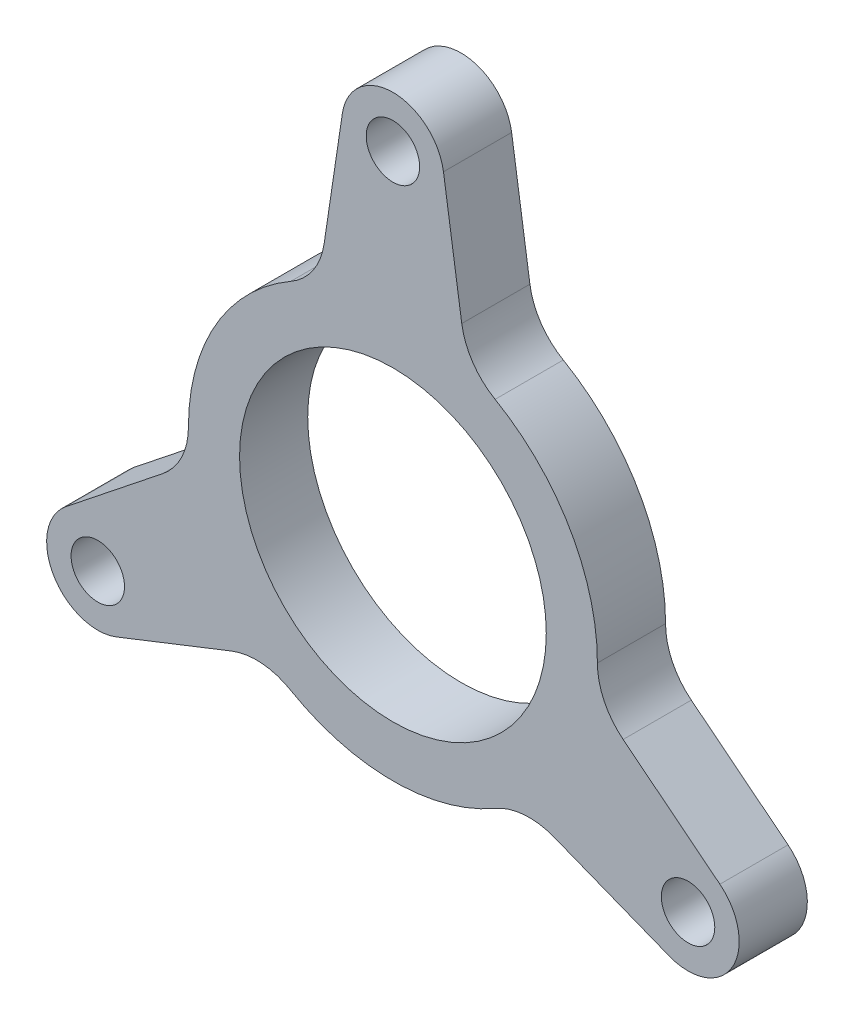
SolidWorks part; units mm, degrees
material "6061-T6 (SS)"
ref_plane "Front Plane" through (0, 0, 0) normal (0, 0, 1) x (1, 0, 0)
ref_plane "Top Plane" through (0, 0, 0) normal (0, 1, 0) x (1, 0, 0)
ref_plane "Right Plane" through (0, 0, 0) normal (1, 0, 0) x (0, 0, -1)
sketch "Sketch2" plane through (0, 0, 0) normal (0, 0, 1) x (1, 0, 0)
  line L3 (-4.7102, 32.4539) -> (-6.9072, 17.7537)
  line L4 (4.7102, 32.4539) -> (6.9072, 17.7537)
  line L5 (30.461, -12.1478) -> (18.8287, -2.8951)
  line L6 (25.7508, -20.3061) -> (11.9216, -14.8586)
  line L7 (-25.7508, -20.3061) -> (-11.9216, -14.8586)
  line L8 (-30.461, -12.1478) -> (-18.8287, -2.8951)
  line L9 (0, 31.75) -> (0, 0) construction
  circle A0 centre (0, 0) radius 14.2875
  circle A1 centre (0, 31.75) radius 2.4892
  circle A2 centre (27.4963, -15.875) radius 2.4892
  circle A3 centre (-27.4963, -15.875) radius 2.4892
  circle A4 centre (27.4963, -15.875) radius 4.7625
  circle A5 centre (0, 31.75) radius 4.7625
  circle A6 centre (-27.4963, -15.875) radius 4.7625
  circle A7 centre (0, 0) radius 19.05
  point P11 (0, 0)
  point P28 (0, 0)
  point P33 (0, 0)
  dimension "D1" = 28.575
  dimension "D2" = 4.9784
  dimension "D6" = 9.525
  dimension "D5" = 38.1
  dimension "D3" = 31.75
  dimension "D7" = 8.5
  dimension "D8" = 8.5
  dimension "D4" = 3
  dimension "D9" = 3
extrude "Boss-Extrude1" add sketch "Sketch2" along normal blind 6.35 contours A7 A0 | A7 A4 | A7 A5 | A7 A6 | A6 A3 | A4 A2 | A5 A1 | A7 | A7 | A7 region at (0, 23.313, 0) region at (0, 36.3778, 0) region at (0, 18.5112, 0) region at (-20.1896, -11.6565, 0) region at (-25.4858, -11.7068, 0) region at (20.1896, -11.6565, 0) region at (31.6646, -13.8645, 0)
fillet "Fillet2" radius 6.35 6 edges at (18.8287, -2.8951, 3.175) (11.9216, -14.8586, 3.175) (-11.9216, -14.8586, 3.175) (-18.8287, -2.8951, 3.175) (-6.9072, 17.7537, 3.175) (6.9072, 17.7537, 3.175)
equation "\"D8@Sketch2\"=\"D7@Sketch2\""
